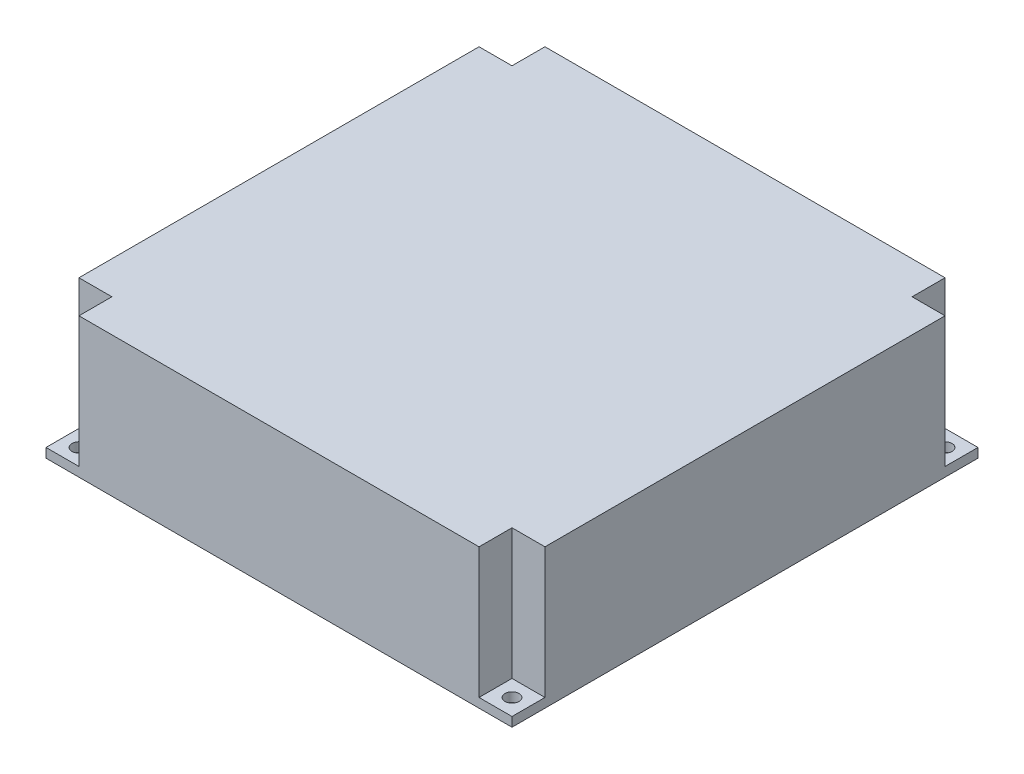
SolidWorks part; units mm, degrees
ref_plane "Alzado" through (0, 0, 0) normal (0, 0, 1) x (1, 0, 0)
ref_plane "Planta" through (0, 0, 0) normal (0, 1, 0) x (1, 0, 0)
ref_plane "Vista lateral" through (0, 0, 0) normal (1, 0, 0) x (0, 0, -1)
sketch "Croquis1" plane through (0, 0, 0) normal (0, 1, 0) x (1, 0, 0)
  line L1 (-50, 50) -> (50, 50)
  line L2 (-50, 50) -> (-50, -50)
  line L3 (-50, -50) -> (50, -50)
  line L4 (50, 50) -> (50, -50)
  line L5 (-50, 50) -> (50, -50) construction
  line L6 (-50, -50) -> (50, 50) construction
  point P0 (0, 0)
  dimension "D1" = 100
  dimension "D2" = 100
extrude "Saliente-Extruir1" add sketch "Croquis1" along normal blind 30
sketch "Croquis2" plane through (0, 30, 0) normal (0, 1, 0) x (1, 0, 0)
  line L0 (-50, -50) -> (50, 50) construction
  line L1 (-50, 50) -> (50, -50) construction
  circle A0 centre (-46.4645, -46.4645) radius 1.5
  circle A1 centre (-46.4645, 46.4645) radius 1.5
  circle A2 centre (46.4645, 46.4645) radius 1.5
  circle A3 centre (46.4645, -46.4645) radius 1.5
  point P19 (0, 0)
  dimension "D1" = 3
  dimension "D2" = 5
  dimension "D3" = 4
extrude "Cortar-Extruir1" cut sketch "Croquis2" against normal blind 38
sketch "Croquis3" plane through (0, 30, 0) normal (0, 1, 0) x (1, 0, 0)
  line L0 (-42.9289, 42.9289) -> (-50, 50) construction
  line L1 (-42.9289, -42.9289) -> (-50, -42.9289)
  line L2 (-42.9289, -42.9289) -> (-42.9289, -50)
  line L3 (-42.9289, -50) -> (-50, -50)
  line L4 (-50, -42.9289) -> (-50, -50)
  line L5 (-42.9289, -42.9289) -> (-50, -50) construction
  line L6 (-42.9289, -50) -> (-50, -42.9289) construction
  line L7 (-50, 42.9289) -> (-42.9289, 50) construction
  line L8 (-42.9289, 42.9289) -> (-50, 42.9289)
  line L9 (-42.9289, 42.9289) -> (-42.9289, 50)
  line L10 (-42.9289, 50) -> (-50, 50)
  line L11 (-50, 42.9289) -> (-50, 50)
  line L12 (42.9289, 42.9289) -> (50, 50) construction
  line L13 (42.9289, 50) -> (50, 42.9289) construction
  line L14 (42.9289, 42.9289) -> (42.9289, 50)
  line L15 (42.9289, 42.9289) -> (50, 42.9289)
  line L16 (50, 42.9289) -> (50, 50)
  line L17 (42.9289, 50) -> (50, 50)
  line L18 (42.9289, -42.9289) -> (50, -50) construction
  line L19 (50, -42.9289) -> (42.9289, -50) construction
  line L20 (42.9289, -42.9289) -> (50, -42.9289)
  line L21 (42.9289, -42.9289) -> (42.9289, -50)
  line L22 (42.9289, -50) -> (50, -50)
  line L23 (50, -42.9289) -> (50, -50)
  point P0 (-46.4645, -46.4645)
  point P10 (-46.4645, 46.4645)
  point P15 (46.4645, 46.4645)
  point P20 (46.4645, -46.4645)
  point P25 (0, 0)
  dimension "D1" = 4
extrude "Cortar-Extruir2" cut sketch "Croquis3" against normal blind 28
shell "Vaciado1" thickness 2 removed face at (46.4645, 0, 47.9645)
